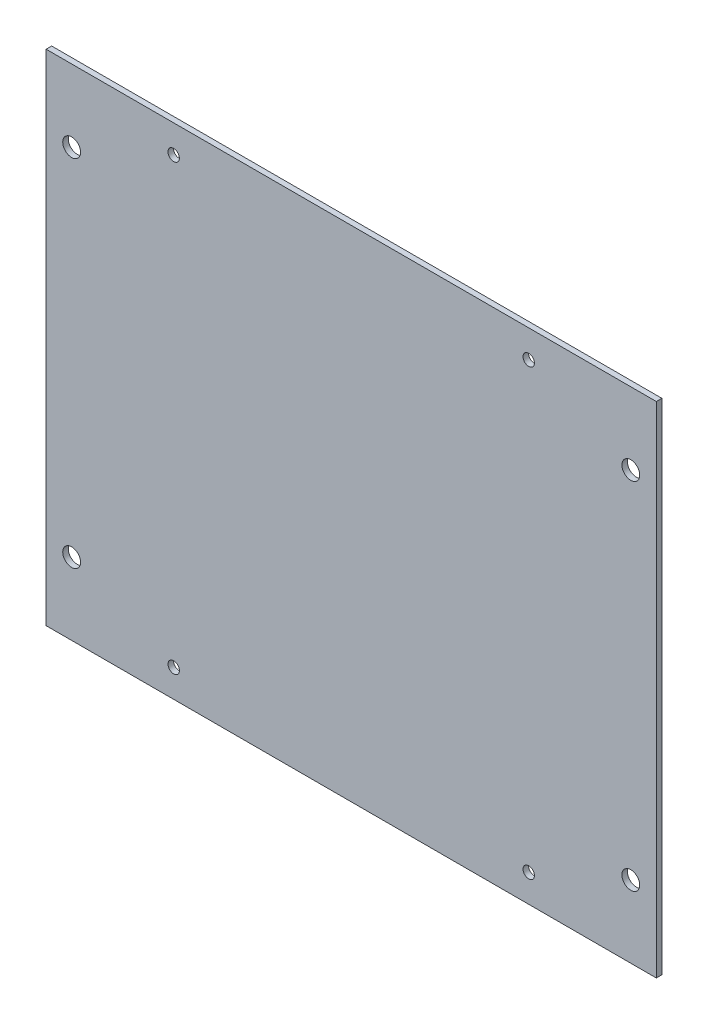
SolidWorks part; units mm, degrees
material "Perspex (TM) GS Acrylic Cast Sheet"
ref_plane "Front Plane" through (0, 0, 0) normal (0, 0, 1) x (1, 0, 0)
ref_plane "Top Plane" through (0, 0, 0) normal (0, 1, 0) x (1, 0, 0)
ref_plane "Right Plane" through (0, 0, 0) normal (1, 0, 0) x (0, 0, -1)
sketch "Sketch1" plane through (0, 0, 0) normal (0, 0, 1) x (1, 0, 0)
  line L1 (-457.2, -304.8) -> (457.2, -304.8)
  line L2 (-457.2, -304.8) -> (-457.2, 304.8)
  line L3 (-457.2, 304.8) -> (457.2, 304.8)
  line L4 (457.2, -304.8) -> (457.2, 304.8)
  line L5 (0, 304.8) -> (0, -304.8) construction
  line L6 (-457.2, 0) -> (457.2, 0) construction
  point P0 (0, 0)
  point P4 (-320.04, 0)
  point P5 (320.04, 0)
  point P6 (0, 213.36)
  point P7 (0, -213.36)
  dimension "Length" = 914.4
  dimension "Width" = 609.6
  dimension "Break" = 137.16
  dimension "D2" = 137.16
  dimension "D1" = 91.44
  dimension "D3" = 91.44
sketch "Sketch2" plane through (0, 0, 0) normal (1, 0, 0) x (0, 0, -1)
  line L0 (-0.7938, -304.8) -> (0.7938, -304.8)
  dimension "Thickness" = 1.5875
sketch "Sketch3" plane through (0, 0, 0) normal (0, 0, 1) x (1, 0, 0)
  line L0 (-457.2, -304.8) -> (-457.2, 304.8) construction
  line L1 (-457.2, -304.8) -> (457.2, -304.8) construction
  line L2 (457.2, -304.8) -> (457.2, 304.8) construction
  line L3 (-457.2, 304.8) -> (457.2, 304.8) construction
  line L4 (-457.2, -304.8) -> (-457.2, 304.8)
  line L5 (-457.2, -304.8) -> (457.2, -304.8)
  line L6 (457.2, -304.8) -> (457.2, 304.8)
  line L7 (-457.2, 304.8) -> (457.2, 304.8)
extrude "Boss-Extrude1" add sketch "Sketch3" along normal mid plane 1.5875
sketch "Sketch4" plane through (0, 0, -0.7937) normal (0, 0, -1) x (-1, 0, 0)
  line L0 (406.2597, -70.2526) -> (231.6347, -70.2526)
  line L1 (231.6347, -70.2526) -> (231.6347, 72.6224)
  line L2 (231.6347, 72.6224) -> (406.2597, 72.6224)
  line L3 (406.2597, 72.6224) -> (406.2597, -70.2526)
extrude "Cut-Extrude1" cut sketch "Sketch4" against normal blind 2.54 flip side to cut
hole_wizard "#4 Clearance Hole1" positions "Sketch9" profile "Sketch10" hole size "#4" standard "ANSI Inch" end condition through all
sketch "Sketch9" plane through (0, 0, -0.7937) normal (0, 0, -1) x (-1, 0, 0)
  line L0 (369.4455, 64.6595) -> (370.0855, 64.6595) construction
  point P0 (268.1472, -62.3151)
  point P6 (369.7655, 64.6595)
  point P16 (369.7472, -62.3151)
  point P28 (268.1472, 64.6849)
sketch "Sketch10" plane through (-268.1472, -62.3151, -0.7937) normal (1, 0, 0) x (0, 1, 0)
  line L0 (0, 0) -> (0, 1.5875)
  line L1 (0, 1.5875) -> (1.6319, 1.5875)
  line L2 (1.6319, 1.5875) -> (1.6319, 0)
  line L5 (1.6319, 0) -> (0, 0)
  line L11 (0, -6.35) -> (0, 107.95) construction
  dimension "Thru Hole Dia." = 3.2639
  dimension "Thru Hole Depth" = 1.5875
hole_wizard "#10 Clearance Hole1" positions "Sketch11" profile "Sketch12" hole size "#10" standard "ANSI Inch" end condition through all
sketch "Sketch11" plane through (0, 0, -0.7937) normal (0, 0, -1) x (-1, 0, 0)
  point P0 (238.9372, -49.6151)
  point P3 (238.9372, 51.9846)
  point P6 (398.9572, 51.9849)
  point P9 (398.9572, -49.6148)
sketch "Sketch12" plane through (-238.9372, -49.6151, -0.7937) normal (1, 0, 0) x (0, 1, 0)
  line L0 (0, 0) -> (0, 1.5875)
  line L1 (0, 1.5875) -> (2.5527, 1.5875)
  line L2 (2.5527, 1.5875) -> (2.5527, 0)
  line L5 (2.5527, 0) -> (0, 0)
  line L11 (0, -6.35) -> (0, 107.95) construction
  dimension "Thru Hole Dia." = 5.1054
  dimension "Thru Hole Depth" = 1.5875
equation "\"D1@Boss-Extrude1\"=\"thickness@sketch2\""
equation "\"Break@Sketch1\" = \"Length@Sketch1\" * 0.15"
equation "\"D2@Sketch1\" = \"Break@Sketch1\""
equation "\"D1@Sketch1\"=\"Width@Sketch1\"*0.15"
equation "\"D3@Sketch1\"=\"D1@Sketch1\""
